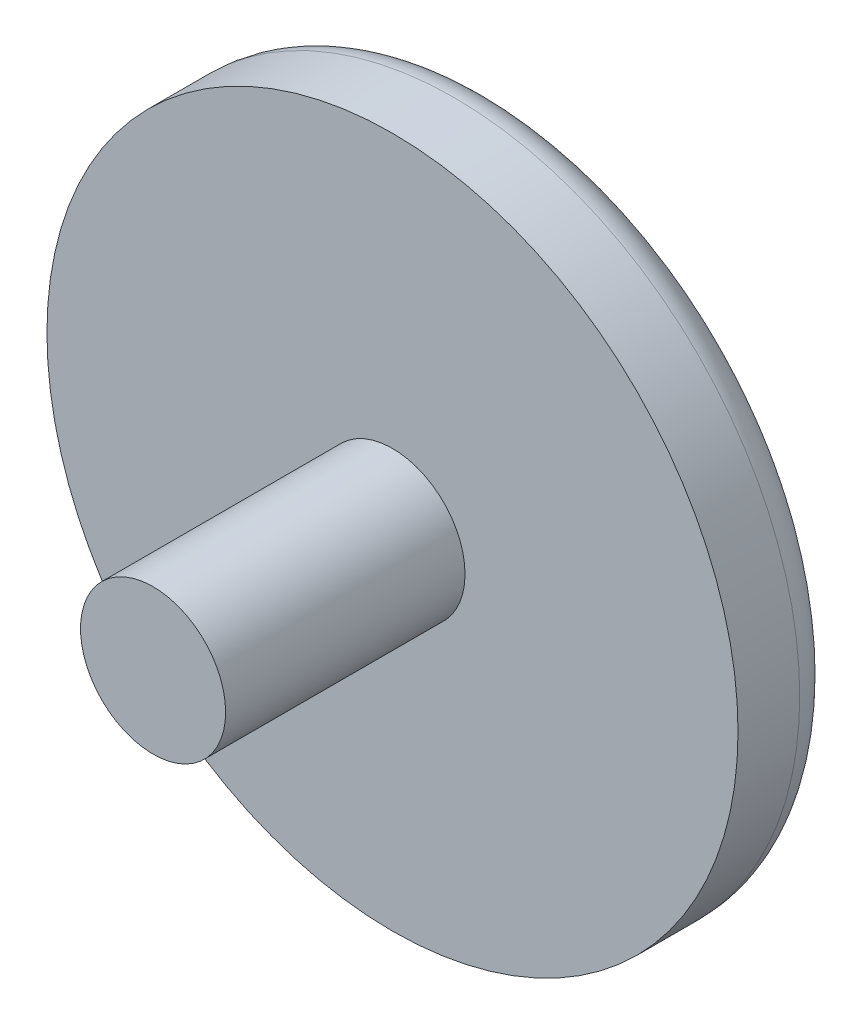
SolidWorks part; units mm, degrees
ref_plane "Front Plane" through (0, 0, 0) normal (0, 0, 1) x (1, 0, 0)
ref_plane "Top Plane" through (0, 0, 0) normal (0, 1, 0) x (1, 0, 0)
ref_plane "Right Plane" through (0, 0, 0) normal (1, 0, 0) x (0, 0, -1)
sketch "Sketch1" plane through (0, 0, 0) normal (0, 0, 1) x (1, 0, 0)
  circle A0 centre (0, 0) radius 14
  dimension "D1" = 28
extrude "Boss-Extrude1" add sketch "Sketch1" along normal blind 4
sketch "Sketch2" plane through (0, 0, 4) normal (0, 0, 1) x (1, 0, 0)
  circle A0 centre (0, 0) radius 2.94
  dimension "D1" = 5.88
extrude "Boss-Extrude2" add sketch "Sketch2" along normal blind 9.7
sketch "Sketch4" plane through (0, 0, 0) normal (0, 0, -1) x (-1, 0, 0)
  circle A0 centre (0, 0) radius 11
  dimension "D1" = 22
extrude "Cut-Extrude1" cut sketch "Sketch4" against normal blind 1
fillet "Fillet1" radius 0.5 2 edges at (-11, 0, 0) (-11, 0, 1)
fillet "Fillet2" radius 1.5 1 edges at (14, 0, 0)
